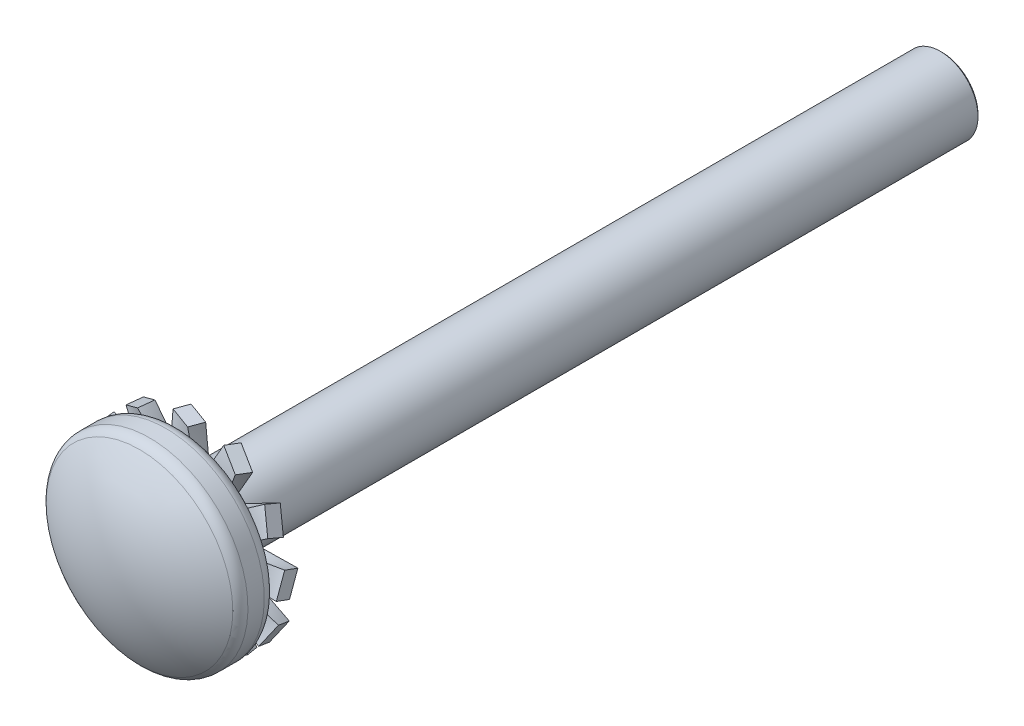
SolidWorks part; units mm, degrees
material "AISI 304"
ref_plane "Front Plane" through (0, 0, 0) normal (0, 0, 1) x (1, 0, 0)
ref_plane "Top Plane" through (0, 0, 0) normal (0, 1, 0) x (1, 0, 0)
ref_plane "Right Plane" through (0, 0, 0) normal (1, 0, 0) x (0, 0, -1)
sketch "Sketch1" plane through (0, 0, 0) normal (0, 0, 1) x (1, 0, 0)
  circle A0 centre (0, 0) radius 2.0828
  dimension "decimal equ" = 4.1656
curve "Helix/Spiral1" pitch 0.7937 height 32.5437 turns 41 parameters "helix length"=32.5437, "pitch"=0.7937
sketch "Sketch2" plane through (0, 0, 0) normal (1, 0, 0) x (0, 0, -1)
  line L0 (0.2977, 2.0828) -> (0.3969, 2.0828)
  line L1 (0.3969, 2.0828) -> (0.6945, 1.5672)
  line L2 (0.2977, 2.0828) -> (0, 1.5672)
  line L3 (0, 1.5672) -> (0.6945, 1.5672)
  line L4 (0.3473, 2.0828) -> (0.3473, 1.5672) construction
  line L6 (0.1488, 1.825) -> (0.5457, 1.825) construction
  line L7 (0, 1.5672) -> (0, 2.0828) construction
  line L8 (0, 2.0828) -> (0, -2.0828) construction
  line L9 (0, 2.0828) -> (0, -2.0828) construction
  point P8 (-3.2742, -2.0828)
  dimension "D1" = 60
  dimension "D3" = 0.0992
  dimension "D4" = 0.3969
  dimension "D2" = 3.2742
sketch "Sketch3" plane through (0, 0, 0) normal (1, 0, 0) x (0, 0, -1)
  line L0 (0, 0) -> (-31.75, 0) construction
  line L1 (0, 1.5672) -> (0.6945, 1.5672) construction
  line L2 (0, 0) -> (-31.75, 0)
  line L3 (0, 0) -> (0, 1.5672)
  line L4 (0, 1.5672) -> (-31.75, 1.5672)
  line L5 (-31.75, 0) -> (-31.75, 1.5672)
  dimension "length" = 31.75
revolve "Revolve1" add sketch "Sketch3" angle 360 about L0
sweep "Sweep1" [suppressed] add profiles "Sketch2" path "Helix/Spiral1"
sketch "Sketch39" plane through (0, 0, 0) normal (0, 0, -1) x (-1, 0, 0)
  circle A0 centre (0, 0) radius 2.0828 construction
  circle A1 centre (0, 0) radius 2.0828
extrude "Extrude5" [suppressed] cut sketch "Sketch39" along normal through all
sketch "Sketch38" plane through (0, 0, 0) normal (0, 0, -1) x (-1, 0, 0)
  circle A2 centre (0, 0) radius 1.4875
  circle A3 centre (0, 0) radius 1.4875
extrude "Extrude6" cut sketch "Sketch38" against normal through all draft 45 flip side to cut
sketch "Sketch10" plane through (0, 0, 0) normal (1, 0, 0) x (0, 0, -1)
  line L0 (0, 0) -> (23.0169, 0) construction
  line L1 (-285.75, 12.7) -> (-31.75, 12.7)
  line L2 (-285.75, 12.7) -> (-285.75, 0)
  line L3 (-285.75, 0) -> (-31.75, 0)
  line L4 (-31.75, 12.7) -> (-31.75, 0)
  line L5 (-31.75, 0) -> (-31.75, 1.5672) construction
  dimension "D1" = 254
  dimension "D2" = 12.7
revolve "Cut-Revolve2" [suppressed] cut sketch "Sketch10" angle 360 about L0
sketch "Sketch41" plane through (0, 0, 0) normal (1, 0, 0) x (0, 0, -1)
  line L0 (-31.75, 2.0828) -> (-31.75, 1.5672)
  line L1 (-31.75, 1.5672) -> (-30.8737, 1.5672)
  line L2 (-30.8737, 1.5672) -> (-30.3581, 2.0828)
  line L3 (-31.75, 2.0828) -> (-30.3581, 2.0828)
  line L4 (0, 1.5672) -> (0.6945, 1.5672) construction
  dimension "D1" = 0.8763
  dimension "D2" = 45
revolve "Cut-Revolve4" [suppressed] cut sketch "Sketch41" angle 360 about L2
sketch "Sketch8" plane through (0, 0, 0) normal (1, 0, 0) x (0, 0, -1)
  line L0 (0, 0) -> (-6.2449, 0) construction
  line L1 (-34.671, 0) -> (-31.75, 0)
  line L2 (-34.671, 0) -> (-34.671, 4.0894)
  line L3 (-34.671, 4.0894) -> (-31.75, 4.0894)
  line L4 (-31.75, 0) -> (-31.75, 4.0894)
  line L5 (-34.671, -4.0894) -> (-31.75, -4.0894) construction
  line L6 (-31.75, 0) -> (-31.75, 1.5672) construction
  dimension "head dia" = 8.1788
  dimension "head height" = 2.921
revolve "Revolve2" add sketch "Sketch8" angle 360 about L0
sketch "Sketch11" plane through (0, 0, 0) normal (1, 0, 0) x (0, 0, -1)
  line L0 (-33.2105, 4.0894) -> (-33.2105, -4.0894) construction
  line L1 (-34.671, 0) -> (-6.8951, 0) construction
  line L2 (-34.671, 4.0894) -> (-31.75, 4.0894) construction
  line L3 (-34.671, 0) -> (-34.671, 4.0894) construction
  line L4 (-32.9549, 4.0894) -> (-32.2758, 4.0894)
  line L6 (-31.75, 0) -> (-31.75, 4.0894) construction
  line L7 (-31.75, 3.5636) -> (-31.115, 3.5636)
  line L8 (-31.115, 3.5636) -> (-31.115, 4.7244)
  line L9 (-31.115, 4.7244) -> (-35.306, 4.7244)
  line L10 (-35.306, 4.7244) -> (-35.306, 0)
  line L11 (-35.306, 0) -> (-34.671, 0)
  arc A0 (-33.3751, 3.8796) -> (-34.671, 0) centre (-28.2156, 0) ccw
  arc A1 (-31.75, 3.5636) -> (-32.2758, 4.0894) centre (-32.2758, 3.5636) ccw
  arc A2 (-33.3751, 3.8796) -> (-32.9549, 4.0894) centre (-32.9549, 3.5636) cw
  dimension "D1" = 0.5258
  dimension "D2" = 0.635
  dimension "D3" = 0.635
  dimension "D4" = 0.635
revolve "Cut-Revolve3" cut sketch "Sketch11" angle 360 about L1
ref_plane "Plane1" through (0, 0, 34.671) normal (0, 0, 1) x (1, 0, 0)
sketch "Sketch12" plane through (0, 0, 34.671) normal (0, 0, 1) x (1, 0, 0)
  line L0 (0.508, 2.3264) -> (0.508, 1.1906)
  line L1 (0.508, 1.1906) -> (1.1906, 0.508) construction
  line L2 (1.1906, 0.508) -> (2.3264, 0.508)
  line L3 (0, 2.3813) -> (0, 0)
  line L4 (0, 0) -> (2.3813, 0)
  line L5 (0, 0) -> (0, 4.0894) construction
  line L6 (0, 0) -> (0.8493, 0.8493) construction
  line L7 (1.1906, 0) -> (1.1906, 1.5633) construction
  line L8 (0.508, 1.1906) -> (0.7079, 0.7079)
  line L9 (1.1906, 0.508) -> (0.7079, 0.7079)
  line L10 (0, 0) -> (0, -1.0114) construction
  line L11 (-0.508, 2.3264) -> (-0.508, 1.1906) construction
  arc A0 (2.3813, 0) -> (2.3264, 0.508) centre (0, 0) ccw
  arc A1 (0.508, 2.3264) -> (0, 2.3813) centre (0, 0) ccw
  arc A2 (-2.3813, 0) -> (-2.3264, 0.508) centre (0, 0) cw construction
  dimension "phillips dia" = 4.7625
  dimension "D2" = 45
  dimension "D4" = 22.5
  dimension "slot width" = 1.016
extrude "Cut-Extrude1" [suppressed] cut sketch "Sketch12" against normal blind 2.4829
draft "Draft3" [suppressed] type of draft neutral plane draft angle 15 neutral plane "Plane1" faces to draft 2 parameters "D1"=15
draft "Draft4" [suppressed] type of draft neutral plane draft angle 5 neutral plane "Plane1" faces to draft 4 parameters "D1"=5
pattern_circular "CirPattern1" [suppressed] count 4 over 360 about axis through (0, 0, 34.671) along (0, 0, -1) of bodies 110
ref_plane "Plane8" through (0, 0, 31.5939) normal (0, 0, -1) x (-1, 0, 0)
sketch "Sketch18" plane through (0, 0, 31.5939) normal (0, 0, 1) x (1, 0, 0)
  line L0 (0, 0) -> (0, 4.064) construction
  line L1 (1.5672, 0) -> (4.064, 0) construction
  circle A0 centre (0, 0) radius 4.064
  circle A1 centre (0, 0) radius 1.5672 construction
  circle A2 centre (0, 0) radius 1.5672 construction
  circle A3 centre (0, 0) radius 2.6908
  circle A4 centre (0, 0) radius 2.0828 construction
  point P8 (2.6908, 0)
  point P10 (0, 2.6908)
  dimension "washer dia." = 8.128
  dimension "D2" = 1.1235
sketch "Sketch21" plane through (0, 0, 31.5939) normal (0, 0, 1) x (1, 0, 0)
  circle A0 centre (0, 0) radius 2.6908
  circle A1 centre (0, 0) radius 1.5672
  circle A2 centre (0, 0) radius 2.0828 construction
extrude "Extrude2" add sketch "Sketch21" against normal blind 0.5842 separate body
ref_plane "Plane9" through (0, 2.6908, 0) normal (0, 1, 0) x (-1, 0, 0)
sketch "Sketch31" plane through (0, 2.6908, 0) normal (0, 1, 0) x (-1, 0, 0)
  line L1 (-0.508, 31.5939) -> (0.508, 31.5939)
  line L2 (-0.508, 31.5939) -> (-0.508, 31.0097)
  line L3 (-0.508, 31.0097) -> (0.508, 31.0097)
  line L4 (0.508, 31.5939) -> (0.508, 31.0097)
  line L5 (-2.6908, 31.0097) -> (2.6908, 31.0097) construction
  line L6 (0, 0) -> (0, 31.5939) construction
  line L7 (0.508, 31.3018) -> (-0.508, 31.3018) construction
  line L8 (0, 31.5939) -> (0, 31.0097) construction
  line L9 (2.6908, 31.5939) -> (-2.6908, 31.5939) construction
  dimension "D1" = 1.016
ref_plane "Plane10" through (0, 4.064, 0) normal (0, 1, 0) x (-1, 0, 0)
sketch "Sketch32" plane through (0, 4.064, 0) normal (0, 1, 0) x (-1, 0, 0)
  line L0 (-0.3775, 31.75) -> (-0.5773, 31.201)
  line L1 (-0.3775, 31.75) -> (0.5773, 31.4025)
  line L2 (-0.5773, 31.201) -> (0.3775, 30.8535)
  line L3 (0.5773, 31.4025) -> (0.3775, 30.8535)
  line L4 (-0.508, 31.5939) -> (-0.508, 31.0097) construction
  line L5 (-0.508, 31.0097) -> (0.508, 31.0097) construction
  line L6 (0.0999, 31.5763) -> (0, 31.3018) construction
  line L7 (0, 31.3018) -> (0.4774, 31.128) construction
  line L8 (0.508, 31.3018) -> (-0.508, 31.3018) construction
  line L9 (0, 0) -> (0, 6.2449) construction
  line L10 (-1.5672, 31.0097) -> (1.5672, 31.0097) construction
  dimension "D1" = 20
sketch "Sketch33" plane through (0, 2.6908, 0) normal (0, 1, 0) x (-1, 0, 0)
  line L1 (1.5672, 31.5939) -> (-1.5672, 31.5939) construction
  line L4 (0.508, 31.5939) -> (-0.508, 31.5939)
  line L5 (0.508, 31.0097) -> (0.508, 31.5939)
  line L6 (-0.508, 31.0097) -> (0.508, 31.0097)
  line L7 (-0.508, 31.5939) -> (-0.508, 31.0097)
  line L8 (0.508, 31.5939) -> (-0.508, 31.5939)
  line L9 (0.508, 31.0097) -> (0.508, 31.5939)
  line L10 (-0.508, 31.0097) -> (0.508, 31.0097)
  line L11 (-0.508, 31.5939) -> (-0.508, 31.0097)
  dimension "D1" = 0
extrude "Extrude3" add sketch "Sketch33" against normal up to next (1.1235 mm away)
loft "Loft2" add profiles "Sketch32", "Sketch31"
pattern_circular "CirPattern4" count 12 over 360 about axis through (0, 0, 31.0097) along (0, 0, 1) of "Loft2", "Extrude3"
sketch "Sketch40" plane through (0, 0, 0) normal (1, 0, 0) x (0, 0, -1)
  line L0 (-31.5939, 4.064) -> (-31.0097, 4.064) construction
  line L1 (-31.5939, -4.064) -> (-31.0097, -4.064) construction
  line L2 (-31.3018, 4.064) -> (-31.3018, -4.064) construction
  line L3 (-31.3018, 0) -> (0, 0) construction
  line L4 (0, -1.4875) -> (0, 1.4875) construction
  line L6 (-31.5939, -5.9931) -> (-31.5939, 5.9931) construction
  dimension "D1" = 0.5842
  dimension "D2" = 8.128
equation "\"D3@Sketch2\" = \"pitch@Helix/Spiral1\"*.125"
equation "\"D4@Sketch2\" = \"pitch@Helix/Spiral1\"*.5"
equation "\"D1@Sketch11\" = \"head height@Sketch8\"*.18"
equation "\"D1@Cut-Extrude1\" = \"head height@Sketch8\"*.85"
equation "\"D1@Sketch31\" = \"washer dia.@Sketch18\"*.125"
equation "\"helix length@Helix/Spiral1\" = \"length@Sketch3\" + \"pitch@Helix/Spiral1\""
equation "\"D1@Sketch38\" = \"pitch@Helix/Spiral1\"*.750"
equation "\"D1@Plane8\" = \"D2@Sketch32\""
equation "\"D2@Sketch18\" = \"D1@Sketch18\"*.45"
equation "\"D2@Sketch2\" = \"pitch@Helix/Spiral1\"*4.125"
equation "\"D1@Sketch40\" = \"washer width@Extrude2\""
equation "\"D2@Sketch40\" = \"washer dia.@Sketch18\""
equation "\"D1@Sketch41\" = \"washer width@Extrude2\"*1.50"
